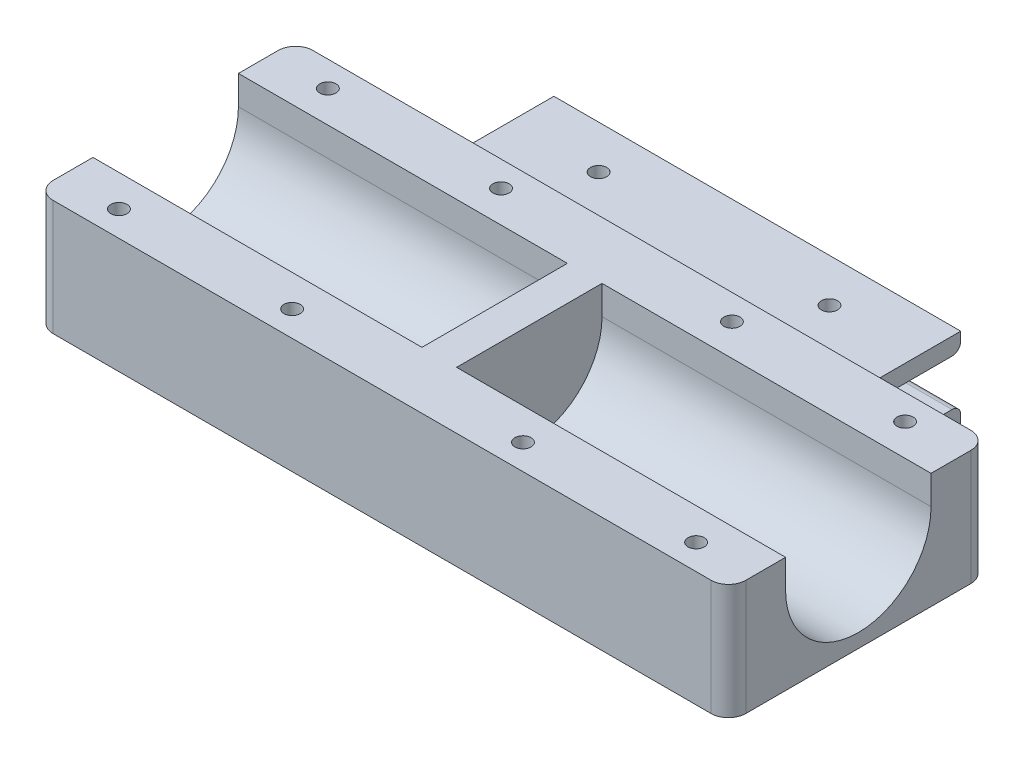
SolidWorks part; units mm, degrees
ref_plane "Front Plane" through (0, 0, 0) normal (0, 0, 1) x (1, 0, 0)
ref_plane "Top Plane" through (0, 0, 0) normal (0, 1, 0) x (1, 0, 0)
ref_plane "Right Plane" through (0, 0, 0) normal (1, 0, 0) x (0, 0, -1)
sketch "Sketch2" plane through (0, 0, 0) normal (0, 1, 0) x (1, 0, 0)
  line L2 (-41.66, -21.8597) -> (-41.66, -66.8597)
  line L3 (-41.66, -66.8597) -> (78.34, -66.8597)
  line L4 (78.34, -21.8597) -> (78.34, -66.8597)
  line L9 (-41.66, -21.8597) -> (-16.9026, -21.8597)
  line L10 (53.5827, -21.8597) -> (78.34, -21.8597)
  line L12 (-16.9026, -21.8597) -> (-16.9026, -1.8597)
  line L13 (-16.9026, -1.8597) -> (53.5827, -1.8597)
  line L14 (53.5827, -21.8597) -> (53.5827, -1.8597)
  dimension "D1" = 20
  dimension "D2" = 45
  dimension "D3" = 120
  dimension "D4" = 70.4853
extrude "Boss-Extrude1" add sketch "Sketch2" along normal blind 20 contours L2 L3 L4 L10 L14 L13 L12 L9
sketch "Sketch3" plane through (78.34, 0, 0) normal (1, 0, 0) x (0, 0, -1)
  circle A8 centre (-44.3597, 15) radius 12.6
  circle A9 centre (-26.8597, 15) radius 1.4
  circle A10 centre (-61.8597, 15) radius 1.4
  line M3 (-21.8597, 20) -> (-66.8597, 20)
sketch "Sketch5" plane through (-41.66, 0, 0) normal (-1, 0, 0) x (0, 0, 1)
  circle A5 centre (44.3597, 15) radius 12.6
  circle A6 centre (26.8597, 15) radius 1.4
  circle A8 centre (61.8597, 15) radius 1.4
  line M3 (66.8597, 20) -> (21.8597, 20)
sketch "Sketch12" plane through (0, 0, 1.8597) normal (0, 0, -1) x (-1, 0, 0)
  line L0 (16.9026, 20) -> (16.9026, 0) construction
  line L1 (-53.5827, 0) -> (16.9026, 0)
  line L2 (-53.5827, 0) -> (-53.5827, 3)
  line L3 (-53.5827, 3) -> (16.9026, 3)
  line L4 (16.9026, 0) -> (16.9026, 3)
  line L6 (-53.5827, 3) -> (16.9026, 3)
  line L18 (-53.5827, 3) -> (16.9026, 3)
  line L19 (-53.5827, 3) -> (-53.5827, 11)
  line L20 (-53.5827, 11) -> (16.9026, 11)
  line L21 (16.9026, 3) -> (16.9026, 11)
  line L22 (-53.5827, 20) -> (16.9026, 20)
  line L23 (-53.5827, 20) -> (-53.5827, 14)
  line L24 (-53.5827, 14) -> (16.9026, 14)
  line L25 (16.9026, 20) -> (16.9026, 14)
  line M5 (-53.5827, 0) -> (16.9026, 0)
  line M6 (16.9026, 0) -> (16.9026, 20)
  line M8 (-53.5827, 20) -> (-53.5827, 0)
  dimension "D1" = 3
  dimension "D2" = 8
  dimension "D3" = 6
extrude "Cut-Extrude1" cut sketch "Sketch3" against normal blind 57 contours A8 M3 region at (78.34, 12.2275, 44.3597)
extrude "Cut-Extrude2" cut sketch "Sketch5" against normal blind 57 contours A5 M3 region at (-41.66, 12.2275, 44.3597)
extrude "Cut-Extrude3" cut sketch "Sketch12" against normal blind 20 contours L24 L25 L22 L23
extrude "Cut-Extrude4" cut sketch "Sketch12<7>" against normal blind 15 and the other way through all flip side to cut contours L3 M8 M5 M6 | L24 L20 M8 M6 region at (18.34, 1.5, 1.8597) region at (18.34, 12.5, 1.8597)
sketch "Sketch12<7>" plane through (0, 0, 1.8597) normal (0, 0, -1) x (-1, 0, 0) same geometry as "Sketch12"
sketch "Sketch16" plane through (-41.66, 0, 0) normal (-1, 0, 0) x (0, 0, 1)
  line L0 (31.7597, 15) -> (31.7597, 20)
  line L1 (21.8597, 20) -> (32.7942, 20) construction
  line L2 (31.7597, 20) -> (56.9597, 20)
  line L3 (55.9251, 20) -> (66.8597, 20) construction
  line L4 (56.9597, 20) -> (56.9597, 15)
  line L5 (56.9597, 15) -> (31.7597, 15)
  arc A0 (32.7942, 20) -> (55.9251, 20) centre (44.3597, 15) ccw construction
  arc A1 (32.7942, 20) -> (55.9251, 20) centre (44.3597, 15) ccw construction
extrude "Cut-Extrude8" cut sketch "Sketch16" against normal blind 57
sketch "Sketch18" plane through (0, 20, 0) normal (0, 1, 0) x (1, 0, 0)
  circle A23 centre (-31.66, -26.2597) radius 1.4
  circle A24 centre (-1.66, -26.2597) radius 1.4
  circle A25 centre (-1.66, -62.4597) radius 1.4
  circle A26 centre (-31.66, -62.4597) radius 1.4
  circle A27 centre (38.34, -62.4597) radius 1.4
  circle A28 centre (68.34, -62.4597) radius 1.4
  circle A29 centre (38.34, -26.2597) radius 1.4
  circle A30 centre (68.34, -26.2597) radius 1.4
extrude "Cut-Extrude11" cut sketch "Sketch18" against normal blind 10
fillet "Fillet2" radius 1 2 edges at (18.34, 3, 16.8597) (18.34, 11, 16.8597)
fillet "Fillet3" radius 1.5 2 edges at (18.34, 3, 1.8597) (18.34, 11, 1.8597)
sketch "Sketch20" plane through (78.34, 0, 0) normal (1, 0, 0) x (0, 0, -1)
  line L0 (-56.9597, 15) -> (-56.9597, 20)
  line L1 (-56.9597, 20) -> (-31.7597, 20)
  line L2 (-31.7597, 20) -> (-31.7597, 15)
  line L3 (-31.7597, 15) -> (-56.9597, 15)
  arc A0 (-55.9251, 20) -> (-32.7942, 20) centre (-44.3597, 15) ccw construction
  arc A1 (-55.9251, 20) -> (-32.7942, 20) centre (-44.3597, 15) ccw construction
extrude "Cut-Extrude12" cut sketch "Sketch20" against normal blind 57
fillet "Fillet5" radius 3 4 edges at (78.34, 10, 66.8597) (78.34, 10, 21.8597) (-41.66, 10, 21.8597) (-41.66, 10, 66.8597)
fillet "Fillet6" radius 4 3 edges at (53.5827, 7, 21.8597) (-16.9026, 7, 21.8597) (18.34, 14, 21.8597)
sketch "Sketch21" plane through (0, 14, 0) normal (0, 1, 0) x (1, 0, 0)
  circle A2 centre (38.34, -9.3597) radius 1.4
  circle A4 centre (-1.66, -9.3597) radius 1.4
extrude "Cut-Extrude13" cut sketch "Sketch21" against normal blind 20
